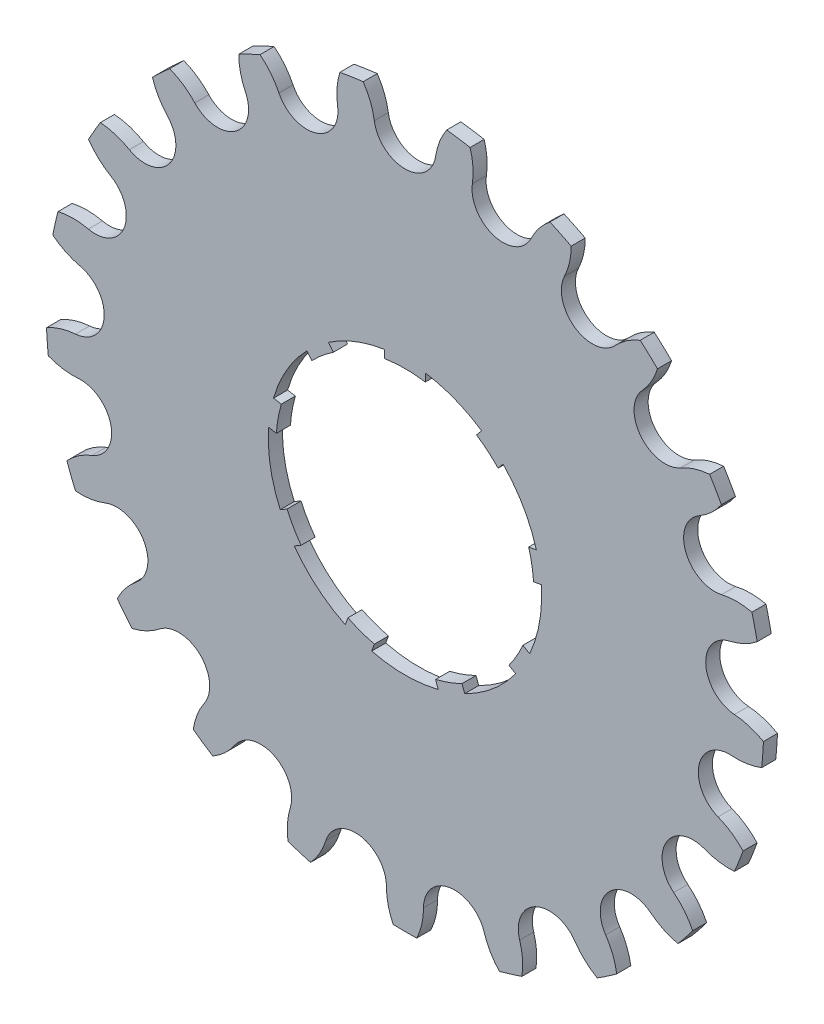
SolidWorks part; units mm, degrees
ref_plane "Alzado" through (0, 0, 0) normal (0, 0, 1) x (1, 0, 0)
ref_plane "Planta" through (0, 0, 0) normal (0, 1, 0) x (1, 0, 0)
ref_plane "Vista lateral" through (0, 0, 0) normal (1, 0, 0) x (0, 0, -1)
sketch "Sk_Disco" plane through (0, 0, 0) normal (0, 0, 1) x (1, 0, 0)
  line L0 (2.6, 17.3058) -> (2.6, 16.2939)
  line L1 (-2.6, 16.2939) -> (-2.6, 17.3058)
  line L2 (-9.8102, 14.4917) -> (-9.1638, 13.7213)
  line L3 (-11.9216, 11.4073) -> (-12.568, 12.1777)
  line L4 (-16.8302, 4.7954) -> (-15.8398, 4.6207)
  line L5 (-16.4649, 1.0754) -> (-17.4553, 1.2501)
  line L6 (-15.9751, -7.1447) -> (-15.1041, -6.6419)
  line L7 (-13.3041, -9.7596) -> (-14.1751, -10.2624)
  line L8 (-7.6451, -15.7418) -> (-7.3011, -14.7968)
  line L9 (-3.9182, -16.028) -> (-4.2622, -16.973)
  line L10 (4.2622, -16.973) -> (3.9182, -16.028)
  line L11 (7.3011, -14.7968) -> (7.6451, -15.7418)
  line L12 (14.1751, -10.2624) -> (13.3041, -9.7596)
  line L13 (15.1041, -6.6419) -> (15.9751, -7.1447)
  line L14 (17.4553, 1.2501) -> (16.4649, 1.0754)
  line L15 (15.8398, 4.6207) -> (16.8302, 4.7954)
  line L16 (12.568, 12.1777) -> (11.9216, 11.4073)
  line L17 (9.1638, 13.7213) -> (9.8102, 14.4917)
  circle A0 centre (0, 0) radius 45.9395
  arc A1 (2.6, 16.2939) -> (-2.6, 16.2939) centre (0, 0) ccw
  arc A2 (-2.6, 17.3058) -> (-9.8102, 14.4917) centre (0, 0) ccw
  arc A3 (-9.1638, 13.7213) -> (-11.9216, 11.4073) centre (0, 0) ccw
  arc A4 (-12.568, 12.1777) -> (-16.8302, 4.7954) centre (0, 0) ccw
  arc A5 (-15.8398, 4.6207) -> (-16.4649, 1.0754) centre (0, 0) ccw
  arc A6 (-17.4553, 1.2501) -> (-15.9751, -7.1447) centre (0, 0) ccw
  arc A7 (-15.1041, -6.6419) -> (-13.3041, -9.7596) centre (0, 0) ccw
  arc A8 (-14.1751, -10.2624) -> (-7.6451, -15.7418) centre (0, 0) ccw
  arc A9 (-7.3011, -14.7968) -> (-3.9182, -16.028) centre (0, 0) ccw
  arc A10 (-4.2622, -16.973) -> (4.2622, -16.973) centre (0, 0) ccw
  arc A11 (3.9182, -16.028) -> (7.3011, -14.7968) centre (0, 0) ccw
  arc A12 (7.6451, -15.7418) -> (14.1751, -10.2624) centre (0, 0) ccw
  arc A13 (13.3041, -9.7596) -> (15.1041, -6.6419) centre (0, 0) ccw
  arc A14 (15.9751, -7.1447) -> (17.4553, 1.2501) centre (0, 0) ccw
  arc A15 (16.4649, 1.0754) -> (15.8398, 4.6207) centre (0, 0) ccw
  arc A16 (16.8302, 4.7954) -> (12.568, 12.1777) centre (0, 0) ccw
  arc A17 (11.9216, 11.4073) -> (9.1638, 13.7213) centre (0, 0) ccw
  arc A18 (9.8102, 14.4917) -> (2.6, 17.3058) centre (0, 0) ccw
  dimension "D1" = 91.879
extrude "Disco" add sketch "Sk_Disco" along normal blind 1.8
sketch "Sk_Hueco" plane through (0, 0, 0) normal (0, 0, 1) x (1, 0, 0)
  line L0 (0, 0) -> (0, 42.6054) construction
  line L1 (0, 0) -> (-12.5582, 40.7125) construction
  line L2 (0, 0) -> (12.5582, 40.7125) construction
  line L3 (0, 42.6054) -> (-12.5582, 40.7125) construction
  line L4 (0, 42.6054) -> (12.5582, 40.7125) construction
  arc A0 (-3.9306, 42.0129) -> (3.9306, 42.0129) centre (0, 42.6054) ccw
  arc A1 (-3.9306, 42.0129) -> (-6.9873, 47.4276) centre (-12.5582, 40.7125) ccw
  arc A2 (6.9873, 47.4276) -> (3.9306, 42.0129) centre (12.5582, 40.7125) ccw
  arc A3 (6.9873, 47.4276) -> (-6.9873, 47.4276) centre (0, 0) ccw
  dimension "D6" = 3.975
  dimension "D7" = 47.9395
  dimension "D1" = 42.6054
  dimension "D2" = 42.6054
  dimension "D3" = 42.6054
  dimension "D4" = 17.143
  dimension "D5" = 17.143
extrude "Hueco_diente" cut sketch "Sk_Hueco" along normal through all
ref_axis "Eje_pinon" through (0, 0, -0.09) along (0, 0, 1)
pattern_circular "Matriz_dientes" count 21 over 360 about axis through (0, 0, -0.09) along (0, 0, 1) of "Hueco_diente"
equation "\"Z\"= 21"
equation "\"p\"= 12.7"
equation "\"Dr\"= 7.75"
equation "\"e\"= 1.8"
equation "\"D\"= \"p\" / sin ( 180 / \"Z\" )"
equation "\"De\"= \"p\" * ( 0.6 + 1 / tan ( 180 / \"Z\" ) )"
equation "\"Di\"= \"D\" - \"Dr\""
equation "\"Ang\"= 360 / \"Z\""
equation "\"D1@Sk_Disco\" = \"De\""
equation "\"D1@Disco\" = \"e\""
equation "\"D1@Sk_Hueco\" = \"D\" / 2"
equation "\"D2@Sk_Hueco\" = \"D\" / 2"
equation "\"D3@Sk_Hueco\" = \"D\" / 2"
equation "\"D4@Sk_Hueco\" = \"Ang\""
equation "\"D5@Sk_Hueco\" = \"Ang\""
equation "\"D6@Sk_Hueco\" = \"Dr\" / 2 + 0.1"
equation "\"D7@Sk_Hueco\" = \"De\" / 2 + 2"
equation "\"D1@Matriz_dientes\" = \"Z\""
